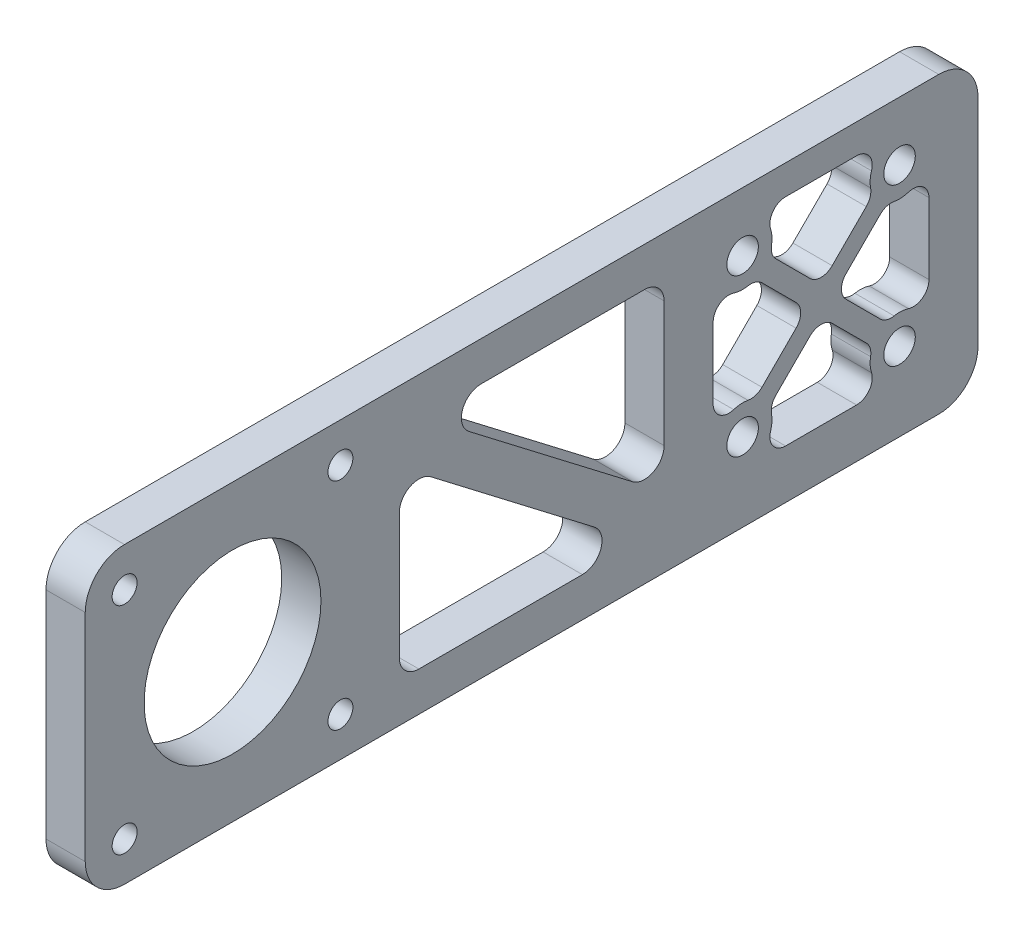
SolidWorks part; units mm, degrees
material "6061-T6 (SS)"
ref_plane "Front" through (0, 0, 0) normal (0, 0, 1) x (1, 0, 0)
ref_plane "Top" through (0, 0, 0) normal (0, 1, 0) x (1, 0, 0)
ref_plane "Right" through (0, 0, 0) normal (1, 0, 0) x (0, 0, -1)
sketch "Sketch1" plane through (0, 0, 0) normal (1, 0, 0) x (0, 0, -1)
  line L0 (0, -23.8125) -> (0, 23.8125)
  line L3 (0, 23.8125) -> (-144.4879, 23.8125)
  line L4 (-144.4879, -23.8125) -> (0, -23.8125)
  line L5 (-144.4879, 23.8125) -> (-144.4879, -23.8125)
  line L6 (-120.65, 23.8125) -> (-120.65, -23.8125) construction
  circle A1 centre (-120.65, 0) radius 14.3129
  point P4 (0, 0)
  dimension "D3" = 28.6258
  dimension "D1" = 9.525
  dimension "D2" = 47.625
  dimension "D5" = 120.65
extrude "Boss-Extrude1" add sketch "Sketch1" along normal blind 6.35
fillet "Fillet1" radius 6.35 4 edges at (3.175, -23.8125, 144.4879) (3.175, 23.8125, 144.4879) (3.175, -23.8125, 0) (3.175, 23.8125, 0)
sketch "Sketch4" plane through (0, 0, 0) normal (-1, 0, 0) x (0, 0, 1)
  point P0 (103.1875, 17.4625)
  point P3 (138.1125, 17.4625)
  point P6 (138.1125, -17.4625)
  point P9 (103.1875, -17.4625)
hole_wizard "#10-32 Tapped Hole1" positions "Sketch4" profile "Sketch3" tap size "#10-32" standard "ANSI Inch" end condition up to next
sketch "Sketch3" plane through (0, 17.4625, 103.1875) normal (0, 1, 0) x (0, 0, 1)
  line L0 (0, 0) -> (0, 6.35)
  line L1 (0, 6.35) -> (2.0193, 6.35)
  line L2 (2.0193, 6.35) -> (2.0193, 0)
  line L5 (2.0193, 0) -> (0, 0)
  line L11 (0, -6.35) -> (0, 107.95) construction
  dimension "Thru Tap Drill Dia." = 4.0386
  dimension "Thru Tap Drill Depth" = 6.35
cosmetic thread "Hole Thread1" parameters "D2"=4.826
cosmetic thread "Hole Thread2" parameters "D2"=4.826
cosmetic thread "Hole Thread3" parameters "D2"=4.826
cosmetic thread "Hole Thread4" parameters "D2"=4.826
sketch "Sketch7" plane through (6.35, 0, 0) normal (1, 0, 0) x (0, 0, -1)
  line L0 (-50.8, 23.8125) -> (-50.8, -23.8125) construction
  line L1 (-6.35, 23.8125) -> (-138.1379, 23.8125) construction
  line L2 (-138.1379, -23.8125) -> (-6.35, -23.8125) construction
  line L4 (0, -17.4625) -> (0, 17.4625) construction
  line L5 (-50.8, -23.8125) -> (-38.1, -11.1125) construction
  line L8 (-12.7, -11.1125) -> (0, -23.8125) construction
  line L9 (0, -17.4625) -> (0, 17.4625) construction
  line L10 (-138.1379, -23.8125) -> (-6.35, -23.8125) construction
  point P0 (-12.7, 14.2875)
  point P2 (-38.1, 14.2875)
  point P4 (-38.1, -11.1125)
  point P6 (-12.7, -11.1125)
  dimension "D1" = 50.8
  dimension "D2" = 25.4
  dimension "D3" = 25.4
  dimension "D4" = 12.7
hole_wizard "#10 Clearance Hole1" positions "Sketch7" profile "Sketch6" hole size "#10" standard "ANSI Inch" end condition up to next
sketch "Sketch6" plane through (6.35, 14.2875, 12.7) normal (0, 1, 0) x (0, 0, -1)
  line L0 (0, 0) -> (0, 6.35)
  line L1 (0, 6.35) -> (2.5527, 6.35)
  line L2 (2.5527, 6.35) -> (2.5527, 0)
  line L5 (2.5527, 0) -> (0, 0)
  line L11 (0, -6.35) -> (0, 107.95) construction
  dimension "Thru Hole Dia." = 5.1054
  dimension "Thru Hole Depth" = 6.35
sketch "Sketch8" plane through (6.35, 0, 0) normal (1, 0, 0) x (0, 0, -1)
  line L0 (-80.4367, 17.4625) -> (-53.975, 17.4625)
  line L1 (-93.6625, 5.9893) -> (-93.6625, -14.2875)
  line L3 (-90.4875, -17.4625) -> (-64.0258, -17.4625)
  line L4 (-50.8, -5.9893) -> (-50.8, 14.2875)
  line L6 (-6.35, 23.8125) -> (-138.1379, 23.8125) construction
  line L7 (-138.1379, -23.8125) -> (-6.35, -23.8125) construction
  line L8 (0, -17.4625) -> (0, 17.4625) construction
  line L9 (-82.3679, 11.7673) -> (-55.9061, -8.5095)
  line L10 (-62.0946, -11.7673) -> (-88.5564, 8.5095)
  line L11 (-93.6625, 12.4221) -> (-89.8002, 17.4625) construction
  line L12 (-38.1, 19.05) -> (-12.7, 19.05)
  line L13 (-7.9375, 14.2875) -> (-7.9375, -11.1125)
  line L14 (-38.1, -15.875) -> (-12.7, -15.875)
  line L15 (-42.8625, 14.2875) -> (-42.8625, -11.1125)
  line L16 (-33.8025, 12.235) -> (-25.4, 3.8326)
  line L17 (-16.9975, -9.06) -> (-25.4, -0.6576)
  line L18 (-16.9975, 12.235) -> (-25.4, 3.8326)
  line L19 (-14.7525, 9.99) -> (-23.1549, 1.5875)
  line L20 (-23.1549, 1.5875) -> (-14.7525, -6.815)
  line L21 (-27.6451, 1.5875) -> (-36.0475, 9.99)
  line L22 (-27.6451, 1.5875) -> (-36.0475, -6.815)
  line L23 (-25.4, -0.6576) -> (-33.8025, -9.06)
  circle A0 centre (-103.1875, 17.4625) radius 2.0193 construction
  arc A1 (-88.5564, 8.5095) -> (-93.6625, 5.9893) centre (-90.4875, 5.9893) ccw
  arc A2 (-93.6625, -14.2875) -> (-90.4875, -17.4625) centre (-90.4875, -14.2875) ccw
  arc A3 (-62.0946, -11.7673) -> (-64.0258, -17.4625) centre (-64.0258, -14.2875) cw
  arc A4 (-55.9061, -8.5095) -> (-50.8, -5.9893) centre (-53.975, -5.9893) ccw
  arc A5 (-53.975, 17.4625) -> (-50.8, 14.2875) centre (-53.975, 14.2875) cw
  arc A6 (-82.3679, 11.7673) -> (-80.4367, 17.4625) centre (-80.4367, 14.2875) cw
  arc A7 (-33.8025, 12.235) -> (-38.1, 19.05) centre (-38.1, 14.2875) ccw
  arc A8 (-14.7525, 9.99) -> (-7.9375, 14.2875) centre (-12.7, 14.2875) ccw
  arc A9 (-16.9975, -9.06) -> (-12.7, -15.875) centre (-12.7, -11.1125) ccw
  arc A10 (-36.0475, -6.815) -> (-42.8625, -11.1125) centre (-38.1, -11.1125) ccw
  arc A11 (-7.9375, -11.1125) -> (-14.7525, -6.815) centre (-12.7, -11.1125) ccw
  arc A12 (-42.8625, 14.2875) -> (-36.0475, 9.99) centre (-38.1, 14.2875) ccw
  arc A13 (-12.7, 19.05) -> (-16.9975, 12.235) centre (-12.7, 14.2875) ccw
  arc A14 (-38.1, -15.875) -> (-33.8025, -9.06) centre (-38.1, -11.1125) ccw
  dimension "D6" = 3.175
  dimension "D7" = 9.525
  dimension "D1" = 6.35
  dimension "D2" = 6.35
  dimension "D3" = 50.8
  dimension "D4" = 9.525
  dimension "D5" = 6.35
  dimension "D9" = 3.175
  dimension "D10" = 3.175
extrude "Cut-Extrude1" cut sketch "Sketch8" against normal through all
fillet "Fillet2" radius 2.54 20 edges at (3.175, 1.5875, 27.6451) (3.175, -6.815, 36.0475) (3.175, -11.1125, 42.8625) (3.175, 14.2875, 42.8625) (3.175, 12.235, 33.8025) (3.175, 19.05, 38.1) (3.175, 19.05, 12.7) (3.175, 12.235, 16.9975) (3.175, 3.8326, 25.4) (3.175, -0.6576, 25.4) (3.175, -9.06, 16.9975) (3.175, -15.875, 12.7) (3.175, -15.875, 38.1) (3.175, -9.06, 33.8025) (3.175, -11.1125, 7.9375) (3.175, -6.815, 14.7525) (3.175, 1.5875, 23.1549) (3.175, 9.99, 14.7525) (3.175, 14.2875, 7.9375) (3.175, 9.99, 36.0475)
